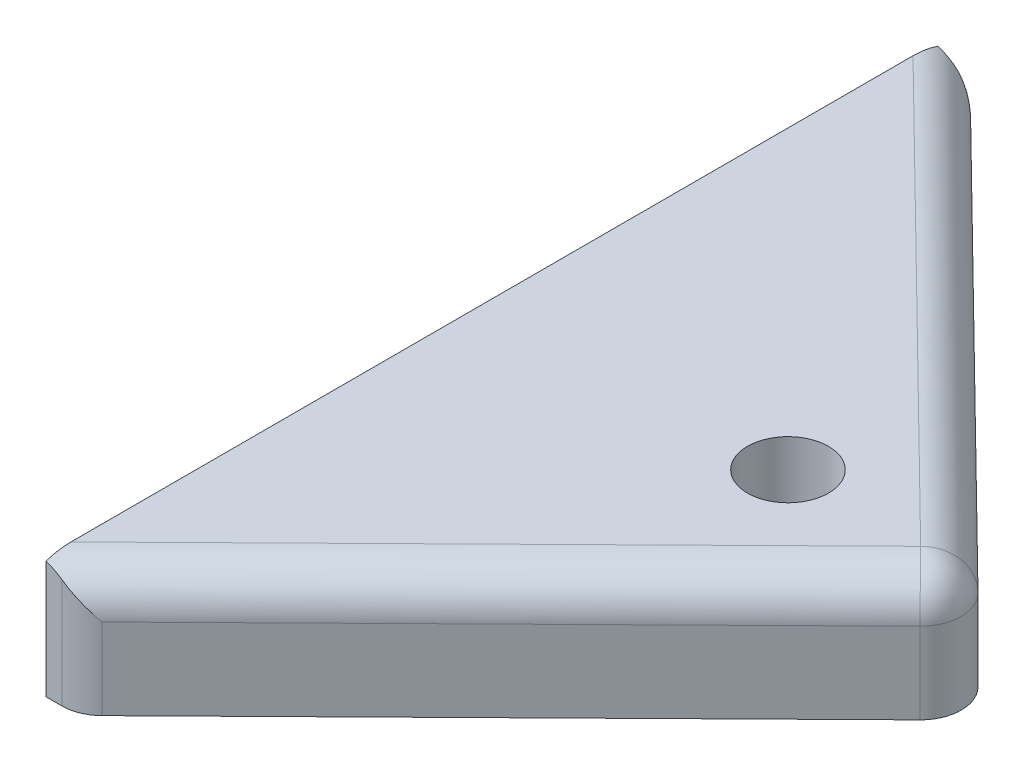
SolidWorks part; units mm, degrees
ref_plane "Front Plane" through (0, 0, 0) normal (0, 0, 1) x (1, 0, 0)
ref_plane "Top Plane" through (0, 0, 0) normal (0, 1, 0) x (1, 0, 0)
ref_plane "Right Plane" through (0, 0, 0) normal (1, 0, 0) x (0, 0, -1)
sketch "Sketch1" plane through (0, 0, 0) normal (0, 1, 0) x (1, 0, 0)
  line L0 (-6, 83.1576) -> (-10, 83.1576)
  line L1 (-10, 83.1576) -> (-10, -26.8424)
  line L2 (-10, -26.8424) -> (-6, -26.8424)
  line L3 (-6, -26.8424) -> (50, 28.1576)
  line L4 (50, 28.1576) -> (-6, 83.1576)
  line L5 (-6, 83.1576) -> (-6, -26.8424) construction
  line L6 (50, 28.1576) -> (-10, 28.1576) construction
  point P2 (-6, 28.1576)
  dimension "D1" = 4
  dimension "D2" = 110
  dimension "D3" = 56
extrude "Boss-Extrude1" add sketch "Sketch1" along normal blind 15
sketch "Sketch2" plane through (0, 0, 0) normal (0, -1, 0) x (1, 0, 0)
  line L0 (-10, -28.1576) -> (35, -28.1576) construction
  line L1 (-10, -83.1576) -> (-10, 26.8424) construction
  line L2 (18, -19.6576) -> (18, -36.6576)
  line L4 (35, -19.6576) -> (35, -36.6576)
  line L7 (18, -19.6576) -> (35, -19.6576)
  line L8 (18, -36.6576) -> (35, -36.6576)
  line L9 (18, -24.1576) -> (-3, -24.1576)
  line L10 (-3, -24.1576) -> (-3, -32.1576)
  line L11 (-3, -32.1576) -> (18, -32.1576)
  point P12 (-3, -28.1576)
  dimension "D1" = 45
  dimension "D2" = 21
  dimension "D3" = 17
  dimension "D4" = 17
  dimension "D5" = 8
extrude "Cut-Extrude2" cut sketch "Sketch2" against normal blind 6 contours L2 L0 L4 L7 | L0 L2 L8 L4 | L10 L0 L2 L9 | L0 L10 L11 L2 region at (7.5, 0, -26.1576) region at (7.5, 0, -30.1576) region at (26.5, 0, -23.9076) region at (26.5, 0, -32.4076)
sketch "Sketch3" plane through (0, 6, 0) normal (0, -1, 0) x (1, 0, 0)
  line L0 (18, -19.6576) -> (35, -36.6576) construction
  line L1 (18, -36.6576) -> (35, -19.6576) construction
  circle A0 centre (26.5, -28.1576) radius 5
  point P10 (26.5, -28.1576)
  dimension "D1" = 10
extrude "Cut-Extrude3" cut sketch "Sketch3" against normal through all
sketch "Sketch5" plane through (-10, 0, 0) normal (-1, 0, 0) x (0, 0, 1)
  line L0 (-83.1576, 7) -> (26.8424, 7) construction
  line L1 (-83.1576, 15) -> (-83.1576, 0) construction
  line L2 (26.8424, 15) -> (26.8424, 0) construction
  line L3 (-83.1576, 15) -> (26.8424, 15) construction
  line L4 (-53.1576, 3.5) -> (-3.1576, 3.5) construction
  line L5 (-28.1576, 3.5) -> (-28.1576, 15) construction
  circle A0 centre (-53.1576, 7) radius 3.5
  circle A1 centre (-3.1576, 7) radius 3.5
  dimension "D1" = 7
  dimension "D2" = 8
  dimension "D3" = 50
extrude "Boss-Extrude2" add sketch "Sketch5" along normal blind 3
fillet "Fillet1" radius 5 5 edges at (22, 15, -0.6576) (22, 15, -55.6576) (-6, 7.5, -83.1576) (-6, 7.5, 26.8424) (50, 7.5, -28.1576)
